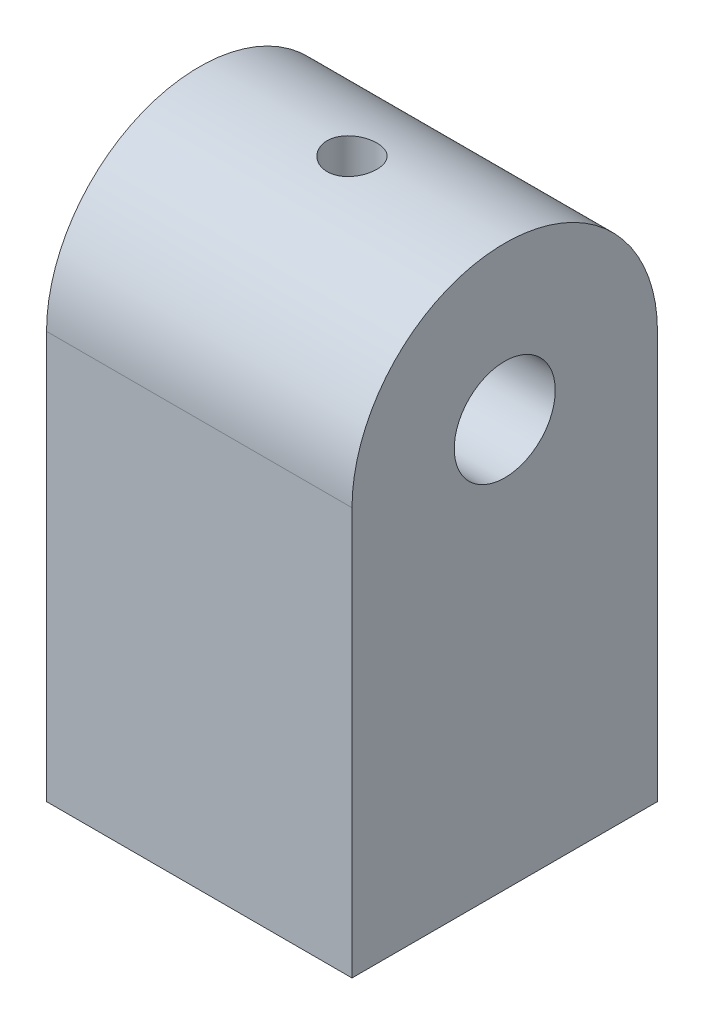
SolidWorks part; units mm, degrees
material "PLA"
ref_plane "Front Plane" through (0, 0, 0) normal (0, 0, 1) x (1, 0, 0)
ref_plane "Top Plane" through (0, 0, 0) normal (0, 1, 0) x (1, 0, 0)
ref_plane "Right Plane" through (0, 0, 0) normal (1, 0, 0) x (0, 0, -1)
sketch "Sketch1" plane through (0, 0, 0) normal (1, 0, 0) x (0, 0, -1)
  circle A0 centre (0, 0) radius 3.15
  circle A1 centre (0, 0) radius 9.525
  dimension "D1" = 6.3
  dimension "D2" = 19.05
extrude "Boss-Extrude1" add sketch "Sketch1" along normal blind 19.05
sketch "Sketch2" plane through (19.05, 0, 0) normal (1, 0, 0) x (0, 0, -1)
  line L0 (9.525, 0) -> (9.525, -25.4)
  line L1 (-9.525, 0) -> (-9.525, -25.4)
  line L2 (9.525, -25.4) -> (-9.525, -25.4)
  circle A0 centre (0, 0) radius 9.525 construction
  circle A1 centre (0, 0) radius 9.525
  circle A2 centre (0, 0) radius 9.525
  circle M4 centre (0, 0) radius 9.525
  dimension "D2" = 25.4
  dimension "D1" = 0
extrude "Boss-Extrude2" add sketch "Sketch2" against normal up to surface (19.05 mm away) contours L0 L2 L1 M4 region at (19.05, -16.3143, 0) up to face at (0, 0, -9.525)
ref_plane "Plane1" through (0, 12.7, 0) normal (0, 1, 0) x (1, 0, 0)
sketch "Sketch3" plane through (0, 12.7, 0) normal (0, 1, 0) x (1, 0, 0)
  line L0 (0, 9.525) -> (0, -9.525) construction
  line L1 (0, 9.525) -> (0, -9.525)
  line L2 (19.05, -9.525) -> (19.05, 9.525) construction
  line L3 (19.05, -9.525) -> (19.05, 9.525)
  line L4 (0, 9.525) -> (19.05, 9.525) construction
  line L5 (0, 9.525) -> (19.05, 9.525)
  line L6 (0, -9.525) -> (19.05, -9.525) construction
  line L7 (0, -9.525) -> (19.05, -9.525)
  circle A0 centre (9.525, 0) radius 1.55
  dimension "D1" = 3.1
extrude "Cut-Extrude1" cut sketch "Sketch3" against normal up to surface (9.9577 mm away) contours A0 region at (9.525, 12.7, 0) up to face at (19.05, 0, -3.15)
